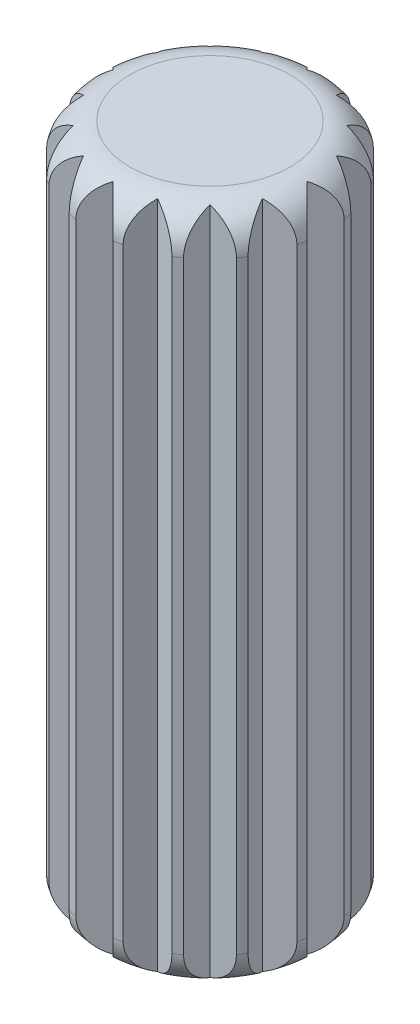
SolidWorks part; units mm, degrees
ref_plane "Front Plane" through (0, 0, 0) normal (0, 0, 1) x (1, 0, 0)
ref_plane "Top Plane" through (0, 0, 0) normal (0, 1, 0) x (1, 0, 0)
ref_plane "Right Plane" through (0, 0, 0) normal (1, 0, 0) x (0, 0, -1)
sketch "Sketch1" plane through (0, 0, 0) normal (0, 1, 0) x (1, 0, 0)
  circle A0 centre (0, 0) radius 2.413
  dimension "D1" = 4.826
extrude "Boss-Extrude1" add sketch "Sketch1" along normal blind 13.97
fillet "Fillet2" radius 0.762 2 edges at (0, 0, 2.413) (0, 13.97, 2.413)
sketch "Sketch2" plane through (0, 13.97, 0) normal (0, 1, 0) x (1, 0, 0)
  line L0 (-0.3851, 2.3821) -> (0, 1.9969)
  line L1 (0, 1.9969) -> (0.3851, 2.3821)
  line L2 (0.5558, 2.3481) -> (0.7642, 1.8449)
  line L3 (0.7642, 1.8449) -> (1.2674, 2.0534)
  line L4 (1.412, 1.9567) -> (1.412, 1.412)
  line L5 (1.412, 1.412) -> (1.9567, 1.412)
  line L6 (2.0534, 1.2674) -> (1.8449, 0.7642)
  line L7 (1.8449, 0.7642) -> (2.3481, 0.5558)
  line L8 (2.3821, 0.3851) -> (1.9969, 0)
  line L9 (1.9969, 0) -> (2.3821, -0.3851)
  line L10 (2.3481, -0.5558) -> (1.8449, -0.7642)
  line L11 (1.8449, -0.7642) -> (2.0534, -1.2674)
  line L12 (1.9567, -1.412) -> (1.412, -1.412)
  line L13 (1.412, -1.412) -> (1.412, -1.9567)
  line L14 (1.2674, -2.0534) -> (0.7642, -1.8449)
  line L15 (0.7642, -1.8449) -> (0.5558, -2.3481)
  line L16 (0.3851, -2.3821) -> (0, -1.9969)
  line L17 (0, -1.9969) -> (-0.3851, -2.3821)
  line L18 (-0.5558, -2.3481) -> (-0.7642, -1.8449)
  line L19 (-0.7642, -1.8449) -> (-1.2674, -2.0534)
  line L20 (-1.412, -1.9567) -> (-1.412, -1.412)
  line L21 (-1.412, -1.412) -> (-1.9567, -1.412)
  line L22 (-2.0534, -1.2674) -> (-1.8449, -0.7642)
  line L23 (-1.8449, -0.7642) -> (-2.3481, -0.5558)
  line L24 (-2.3821, -0.3851) -> (-1.9969, 0)
  line L25 (-1.9969, 0) -> (-2.3821, 0.3851)
  line L26 (-2.3481, 0.5558) -> (-1.8449, 0.7642)
  line L27 (-1.8449, 0.7642) -> (-2.0534, 1.2674)
  line L28 (-1.9567, 1.412) -> (-1.412, 1.412)
  line L29 (-1.412, 1.412) -> (-1.412, 1.9567)
  line L30 (-1.2674, 2.0534) -> (-0.7642, 1.8449)
  line L31 (-0.7642, 1.8449) -> (-0.5558, 2.3481)
  arc A0 (0.3851, 2.3821) -> (-0.3851, 2.3821) centre (0, 0) ccw
  arc A1 (1.2674, 2.0534) -> (0.5558, 2.3481) centre (0, 0) ccw
  circle A2 centre (0, 0) radius 2.413 construction
  arc A3 (1.9567, 1.412) -> (1.412, 1.9567) centre (0, 0) ccw
  arc A4 (2.3481, 0.5558) -> (2.0534, 1.2674) centre (0, 0) ccw
  arc A5 (2.3821, -0.3851) -> (2.3821, 0.3851) centre (0, 0) ccw
  arc A6 (2.0534, -1.2674) -> (2.3481, -0.5558) centre (0, 0) ccw
  arc A7 (1.412, -1.9567) -> (1.9567, -1.412) centre (0, 0) ccw
  arc A8 (0.5558, -2.3481) -> (1.2674, -2.0534) centre (0, 0) ccw
  arc A9 (-0.3851, -2.3821) -> (0.3851, -2.3821) centre (0, 0) ccw
  arc A10 (-1.2674, -2.0534) -> (-0.5558, -2.3481) centre (0, 0) ccw
  arc A11 (-1.9567, -1.412) -> (-1.412, -1.9567) centre (0, 0) ccw
  arc A12 (-2.3481, -0.5558) -> (-2.0534, -1.2674) centre (0, 0) ccw
  arc A13 (-2.3821, 0.3851) -> (-2.3821, -0.3851) centre (0, 0) ccw
  arc A14 (-2.0534, 1.2674) -> (-2.3481, 0.5558) centre (0, 0) ccw
  arc A15 (-1.412, 1.9567) -> (-1.9567, 1.412) centre (0, 0) ccw
  arc A16 (-0.5558, 2.3481) -> (-1.2674, 2.0534) centre (0, 0) ccw
  point P6 (0, 0)
  point P54 (0, 0)
  dimension "D1" = 90
  dimension "D2" = 16
extrude "Cut-Extrude1" cut sketch "Sketch2" against normal through all
